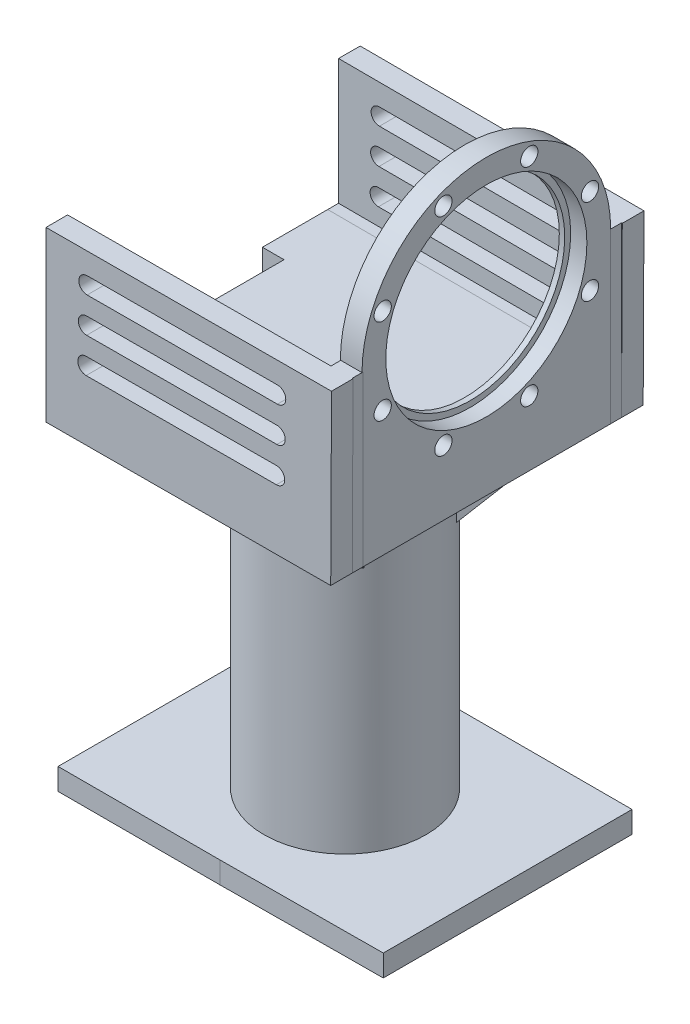
SolidWorks part; units mm, degrees
material "3d打印 35%"
ref_plane "前视基准面" through (0, 0, 0) normal (0, 0, 1) x (1, 0, 0)
ref_plane "上视基准面" through (0, 0, 0) normal (0, 1, 0) x (1, 0, 0)
ref_plane "右视基准面" through (0, 0, 0) normal (1, 0, 0) x (0, 0, -1)
other "Configuration Table"
sketch "草图1" plane through (0, 0, 0) normal (1, 0, 0) x (0, 0, -1)
  line L0 (0, 0) -> (0, 41.2915) construction
  line L1 (0, 0) -> (13.5654, 32.7498) construction
  line L2 (0, 0) -> (-23, 0)
  line L3 (-23, 0) -> (-23, -23.2)
  line L4 (-23, -23.2) -> (23, -23.2)
  line L5 (23, -23.2) -> (23, 0)
  circle A0 centre (0, 0) radius 23
  circle A1 centre (0, 0) radius 20.75 construction
  circle A2 centre (0, 0) radius 15 construction
  circle A3 centre (0, 0) radius 18.6
  circle A4 centre (7.9422, 19.1743) radius 1.6
  circle A5 centre (19.1743, 7.9422) radius 1.6
  circle A6 centre (19.1743, -7.9422) radius 1.6
  circle A7 centre (7.9422, -19.1743) radius 1.6
  circle A8 centre (-7.9422, -19.1743) radius 1.6
  circle A9 centre (-19.1743, -7.9422) radius 1.6
  circle A10 centre (-19.1743, 7.9422) radius 1.6
  circle A11 centre (-7.9422, 19.1743) radius 1.6
  circle A12 centre (0, 0) radius 17.5
  point P27 (0, 0)
  dimension "D1" = 8
extrude "凸台-拉伸1" add sketch "草图1" along normal blind 4 contours A0 L3 L4 L5 | A3 A0 A11 A10 A9 A8 A7 A6 A5 A4 region at (0, 22.3495, 0) region at (0, -23.0515, 0)
extrude "凸台-拉伸2" add sketch "草图1<3>" along normal blind 1 contours A12 A3 region at (0, 18.0739, 0)
sketch "草图1<3>" plane through (0, 0, 0) normal (1, 0, 0) x (0, 0, -1) same geometry as "草图1"
sketch "草图2" plane through (0, -23.2, 0) normal (0, -1, 0) x (1, 0, 0)
  line L0 (4, 23) -> (-48.4998, 23)
  line L1 (-48.4998, 23) -> (-48.4998, -23.1597)
  line L2 (-48.4998, -23.1597) -> (4, -23)
  line L3 (4, -23) -> (4, 23)
  line L4 (-48.4998, -0.0798) -> (-44.4998, -0.0798) construction
  line L5 (-44.4998, 10.9202) -> (-44.4998, -11.0798)
  line L6 (-44.4998, 10.9202) -> (-48.4998, 10.9202)
  line L7 (-44.4998, -11.0798) -> (-48.4998, -11.0798)
  point P11 (-44.4998, -0.0798)
  line M7 (0, 23) -> (0, -23)
  line M8 (0, -23) -> (4, -23)
  line M9 (4, -23) -> (4, 23)
  line M10 (4, 23) -> (0, 23)
extrude "凸台-拉伸3" add sketch "草图2" along normal blind 8 contours L5 L7 L1 L2 L0 L6 M8 M7 | M10 M7 M8 M9 region at (2, -23.2, 0) region at (-23.3512, -23.2, -0.0417)
sketch "草图3" plane through (-44.4998, 0, 0) normal (-1, 0, 0) x (0, 0, 1)
  line L0 (-0.0798, -31.2) -> (-0.0798, -23.2)
  line L1 (10.9202, -31.2) -> (-11.0798, -31.2) construction
  line L2 (10.9202, -23.2) -> (-11.0798, -23.2) construction
  line L3 (-6.0798, -27.2) -> (5.9202, -27.2) construction
  line L4 (23, -23.2) -> (-23, -23.2) construction
  circle A0 centre (5.9202, -27.2) radius 1.85
  circle A1 centre (-6.0798, -27.2) radius 1.85
  circle A2 centre (-6.0798, -27.2) radius 2
  circle A3 centre (5.9202, -27.2) radius 2
  point P9 (-0.0798, -27.2)
extrude "切除-拉伸1" cut sketch "草图3" against normal blind 5 contours A1 | A0 region at (-44.4998, -27.2, 5.9202) region at (-44.4998, -27.2, -6.0798)
chamfer "倒角2" distance 0.4 angle 45 2 edges at (-44.4998, -27.2, 7.7702) (-44.4998, -27.2, -4.2298)
sketch "草图4" plane through (0.07, 0, -23.012) normal (0.003, 0, -1) x (-1, 0, -0.003)
  line L0 (-3.93, 0) -> (0, 0)
  line L1 (0, 0) -> (0, -23.2)
  line L2 (48.57, -23.2) -> (-3.93, -23.2) construction
  line L3 (0, -23.2) -> (48.57, -23.2)
  line L4 (48.57, -23.2) -> (48.57, -31.2)
  line L5 (48.57, -31.2) -> (-3.93, -31.2)
  line L6 (-3.93, -31.2) -> (-3.93, 0)
extrude "凸台-拉伸7" add sketch "草图4" along direction (0, 0, 1) on the side of the normal blind 2 separate body
sketch "草图5" plane through (0.0761, 0, -25.0119) normal (0.003, 0, -1) x (-1, 0, -0.003)
  line L0 (-4.0699, 0) -> (-3.9239, -31.2)
  line L1 (-3.9239, -31.2) -> (48.5761, -31.2)
  line L2 (48.5761, -31.2) -> (48.5761, 0)
  line L3 (48.5761, 0) -> (-4.0699, 0)
  line L4 (5.907, -5.5052) -> (40.9915, -5.5052) construction
  line L5 (5.907, -3.964) -> (40.9915, -3.964)
  line L6 (5.907, -7.0464) -> (40.9915, -7.0464)
  line L7 (6.0005, -12.0045) -> (41.085, -12.0045) construction
  line L8 (6.0005, -10.4633) -> (41.085, -10.4633)
  line L9 (6.0005, -13.5457) -> (41.085, -13.5457)
  line L10 (6.094, -18.5038) -> (41.1784, -18.5038) construction
  line L11 (6.094, -16.9627) -> (41.1784, -16.9627)
  line L12 (6.094, -20.045) -> (41.1784, -20.045)
  arc A0 (5.907, -3.964) -> (5.907, -7.0464) centre (5.907, -5.5052) ccw
  arc A1 (40.9915, -7.0464) -> (40.9915, -3.964) centre (40.9915, -5.5052) ccw
  arc A2 (6.0005, -10.4633) -> (6.0005, -13.5457) centre (6.0005, -12.0045) ccw
  arc A3 (41.085, -13.5457) -> (41.085, -10.4633) centre (41.085, -12.0045) ccw
  arc A4 (6.094, -16.9627) -> (6.094, -20.045) centre (6.094, -18.5038) ccw
  arc A5 (41.1784, -20.045) -> (41.1784, -16.9627) centre (41.1784, -18.5038) ccw
  point P9 (23.4493, -5.5052)
  point P18 (23.5427, -12.0045)
  point P25 (23.6362, -18.5038)
  dimension "D1" = 3
extrude "凸台-拉伸8" add sketch "草图5" along normal blind 4
mirror "镜向3" about plane through (0, 0, 0) normal (0, 0, 1) of bodies 111
move or copy body "实体-移动/复制1" bodies to move or copy 112 copy no translate (0, 0, -0.2) parameters "D1"=0, "D2"=0, "D3"=0.2
sketch "草图6" plane through (0, -31.2, 0) normal (0, -1, 0) x (1, 0, 0)
  line L0 (-22.2377, 28.8798) -> (-22.2377, -29.0798) construction
  line L1 (4.0122, 28.8) -> (-48.4876, 28.9597) construction
  line L2 (4.0122, -29) -> (-48.4876, -29.1597) construction
  line L3 (-44.4998, -0.0798) -> (4, 0) construction
  line L4 (-44.4998, 10.9202) -> (-44.4998, -11.0798) construction
  line L5 (4, -23) -> (4, 23) construction
  circle A0 centre (-22.2377, -0.1) radius 10
  circle A1 centre (-22.2377, -0.1) radius 15
extrude "凸台-拉伸9" add sketch "草图6" along normal blind 60
sketch "草图10" plane through (0, -31.2, 0) normal (0, -1, 0) x (-1, 0, 0)
  line L0 (22.2377, 29.0798) -> (22.2377, -28.8798)
  line L1 (-4.0122, 29) -> (48.4876, 29.1597) construction
  line L2 (-4.0122, -28.8) -> (48.4876, -28.9597) construction
  line L3 (5.2826, 14.8911) -> (39.1928, -14.6911) construction
  line L4 (5.2826, -16.8551) -> (39.1928, 17.0551) construction
  point P9 (22.2377, 0.1)
  point P13 (22.2377, 0.1)
ref_plane "基准面3" through (-22.2377, 0, 0) normal (-1, 0, 0) x (0, 0, 1)
ref_plane "基准面4" through (-9.6595, 0, -11.0728) normal (0.6574, 0, 0.7536) x (-0.7536, 0, 0.6574)
sketch "草图12" plane through (-9.6595, 0, -11.0728) normal (0.6574, 0, 0.7536) x (-0.7536, 0, 0.6574)
  line L0 (1.6917, 45.991) -> (-13.0993, 31.2)
  line L1 (1.6917, 91.2) -> (1.6917, 31.2) construction
  line L2 (-18.134, 31.2) -> (12.1055, 31.2) construction
rib "筋24" sketch "草图12" sketch "草图12" thickness 5 extrusion direction parallel to sketch draft on no parameters "D1"=5
pattern_circular "阵列(圆周)13" count 2 every 180 about axis through (-22.2377, -91.2, -0.1) along (0, 1, 0) of "筋24"
ref_plane "基准面5" through (-11.0689, 0, 11.0689) normal (-0.7071, 0, 0.7071) x (-0.7071, 0, -0.7071)
sketch "草图13" plane through (-11.0689, 0, 11.0689) normal (-0.7071, 0, 0.7071) x (-0.7071, 0, -0.7071)
  line L0 (0.7951, 45.2745) -> (-13.2793, 31.2)
  line L1 (0.7951, 91.2) -> (0.7951, 31.2) construction
  line L2 (-23.2017, 31.2) -> (13.8083, 31.2) construction
rib "筋25" sketch "草图13" sketch "草图13" thickness 5 extrusion direction parallel to sketch draft on no parameters "D1"=5
pattern_circular "阵列(圆周)14" count 2 every 180 about axis through (-22.2377, -91.2, -0.1) along (0, 1, 0) of "筋25"
sketch "草图14" plane through (0.0876, 0, 28.8119) normal (0.003, 0, 1) x (1, 0, -0.003)
  line L0 (-48.5695, -31.2) -> (3.9245, -31.2)
sketch "草图16" plane through (0, -91.2, 0) normal (0, -1, 0) x (1, 0, 0)
  line L0 (-22.2255, -23.2) -> (-22.2499, 23) construction
  line L8 (4, 23) -> (-48.4998, 23) construction
  line L10 (-22.2499, 23) -> (7.7495, 22.8101)
  line L11 (7.7495, 22.8101) -> (7.7495, -23.2)
  line L12 (7.7495, -23.2) -> (-22.2255, -23.2)
  line L13 (-22.2255, -23.2) -> (-52.2255, -23.2)
  line L14 (-52.2255, -23.2) -> (-52.2255, 23)
  line L15 (-52.2255, 23) -> (-22.2499, 23)
  point P6 (-22.2377, -0.1)
extrude "凸台-拉伸10" add sketch "草图16" along normal blind 4
